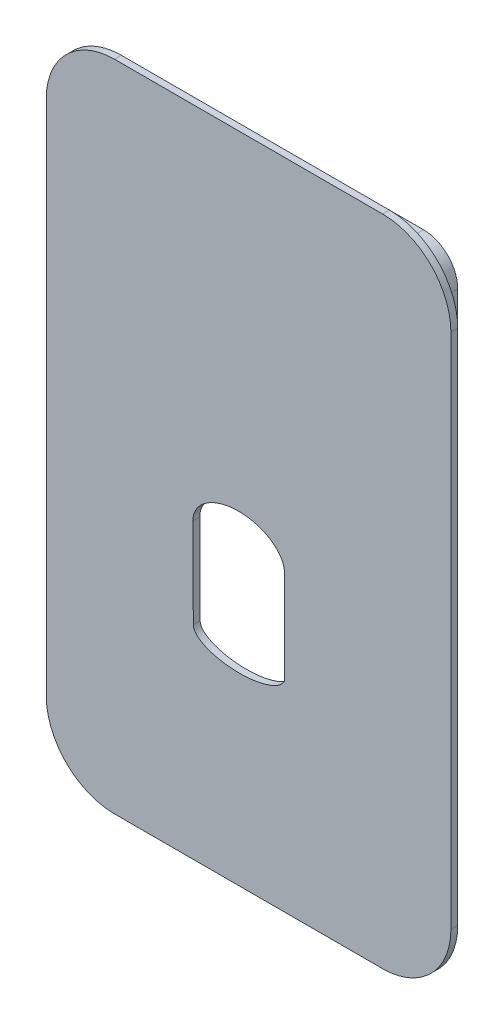
SolidWorks part; units mm, degrees
ref_plane "Front Plane" through (0, 0, 0) normal (0, 0, 1) x (1, 0, 0)
ref_plane "Top Plane" through (0, 0, 0) normal (0, 1, 0) x (1, 0, 0)
ref_plane "Right Plane" through (0, 0, 0) normal (1, 0, 0) x (0, 0, -1)
sketch "Sketch1" plane through (0, 0, 0) normal (0, 0, 1) x (1, 0, 0)
  line L4 (-48.5562, 95.1688) -> (29.9609, 95.1688)
  line L5 (49.9609, 75.1688) -> (49.9609, -76.2545)
  line L6 (-48.5561, -96.2545) -> (29.9609, -96.2545)
  line L7 (-68.5562, 75.1688) -> (-68.5561, -76.2545)
  line L8 (-48.5562, 85.1688) -> (29.9609, 85.1688)
  line L9 (39.9609, 75.1688) -> (39.9609, -44.9339)
  line L11 (-58.5562, 75.1688) -> (-58.5561, -44.9339)
  line L12 (-48.5562, 83.1688) -> (29.9609, 83.1688)
  line L13 (37.9609, 75.1688) -> (37.9609, -44.9339)
  line L15 (-56.5562, 75.1688) -> (-56.5561, -44.9339)
  line L16 (-48.5561, -52.9339) -> (29.9609, -52.9339)
  line L17 (-56.5562, 75.1688) -> (-56.5561, -76.2545) construction
  line L18 (-58.5562, 75.1688) -> (-58.5561, -76.2545) construction
  line L19 (-48.5561, -84.2545) -> (29.9609, -84.2545) construction
  line L20 (-48.5561, -86.2545) -> (29.9609, -86.2545) construction
  line L21 (37.9609, 75.1688) -> (37.9609, -76.2545) construction
  line L22 (39.9609, 75.1688) -> (39.9609, -76.2545) construction
  line L24 (-48.5561, -54.9339) -> (29.9609, -54.9339)
  arc A0 (49.9609, -76.2545) -> (29.9609, -96.2545) centre (29.9609, -76.2545) cw
  arc A1 (29.9609, 95.1688) -> (49.9609, 75.1688) centre (29.9609, 75.1688) cw
  arc A2 (-48.5562, 95.1688) -> (-68.5562, 75.1688) centre (-48.5562, 75.1688) ccw
  arc A3 (-68.5561, -76.2545) -> (-48.5561, -96.2545) centre (-48.5561, -76.2545) ccw
  arc A4 (29.9609, 85.1688) -> (39.9609, 75.1688) centre (29.9609, 75.1688) cw
  arc A7 (-48.5562, 85.1688) -> (-58.5562, 75.1688) centre (-48.5562, 75.1688) ccw
  arc A8 (29.9609, 83.1688) -> (37.9609, 75.1688) centre (29.9609, 75.1688) cw
  arc A11 (-48.5562, 83.1688) -> (-56.5562, 75.1688) centre (-48.5562, 75.1688) ccw
  arc A12 (-58.5561, -76.2545) -> (-48.5561, -86.2545) centre (-48.5561, -76.2545) ccw construction
  arc A13 (-56.5561, -76.2545) -> (-48.5561, -84.2545) centre (-48.5561, -76.2545) ccw construction
  arc A14 (39.9609, -76.2545) -> (29.9609, -86.2545) centre (29.9609, -76.2545) cw construction
  arc A15 (37.9609, -76.2545) -> (29.9609, -84.2545) centre (29.9609, -76.2545) cw construction
  arc A16 (-56.5561, -44.9339) -> (-48.5561, -52.9339) centre (-48.5561, -44.9339) ccw
  arc A17 (37.9609, -44.9339) -> (29.9609, -52.9339) centre (29.9609, -44.9339) cw
  arc A18 (29.9609, -54.9339) -> (39.9609, -44.9339) centre (29.9609, -44.9339) ccw
  arc A19 (-48.5561, -54.9339) -> (-58.5561, -44.9339) centre (-48.5561, -44.9339) cw
  point P40 (-58.5562, -54.9339)
  point P41 (39.9609, -54.7236)
  point P43 (-58.3001, -54.9339)
  dimension "D1" = 20
  dimension "D2" = 20
  dimension "D5" = 8
  dimension "D6" = 8
  dimension "D7" = 10
  dimension "D3" = 10
  dimension "D4" = 2
extrude "Boss-Extrude1" add sketch "Sketch1" along normal blind 2 contours A2 L7 A3 L6 A0 L5 A1 L4
extrude "Boss-Extrude2" add sketch "Sketch1<3>" against normal blind 10
sketch "Sketch1<3>" plane through (0, 0, 0) normal (0, 0, 1) x (1, 0, 0) same geometry as "Sketch1"
sketch "Sketch3" plane through (0, 0, 0) normal (0, 0, -1) x (-1, 0, 0)
  line L0 (25.4894, -36.7008) -> (25.5958, -10.4174)
  line L1 (-1.2493, -10.4166) -> (-1.2531, -37.5275)
  ellipse E0 centre (12.0437, -36.7008) end of major axis (-1.4019, -36.7008) minor radius 5.5714 (-1.2531, -37.5275) -> (25.4894, -36.7008) ccw
  ellipse E1 centre (12.1733, -10.4174) end of major axis (25.5958, -10.4174) minor radius 9.1217 (25.5958, -10.4174) -> (-1.2493, -10.4166) ccw
  point P0 (12.0437, -42.2722)
extrude "Cut-Extrude1" cut sketch "Sketch3" against normal through all both and the other way through all
